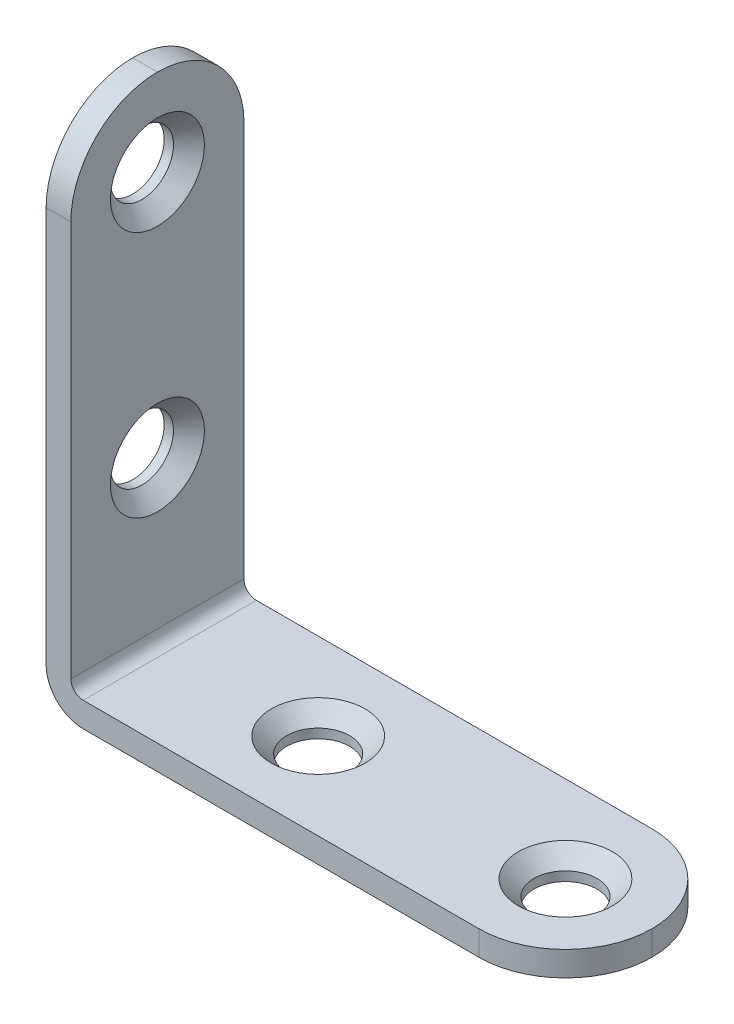
SolidWorks part; units mm, degrees
material "Acier non allié"
ref_plane "Plan de face" through (0, 0, 0) normal (0, 0, 1) x (1, 0, 0)
ref_plane "Plan de dessus" through (0, 0, 0) normal (0, 1, 0) x (1, 0, 0)
ref_plane "Plan de droite" through (0, 0, 0) normal (1, 0, 0) x (0, 0, -1)
sketch "Esquisse1" plane through (0, 0, 0) normal (0, 0, 1) x (1, 0, 0)
  line L0 (0, 3) -> (0, 42)
  line L1 (3, 0) -> (42, 0)
  line L2 (3, 2) -> (42, 2)
  line L3 (2, 3) -> (2, 42)
  line L4 (0, 42) -> (2, 42)
  line L5 (42, 2) -> (42, 0)
  arc A0 (0, 3) -> (3, 0) centre (3, 3) ccw
  arc A1 (2, 3) -> (3, 2) centre (3, 3) ccw
  point P6 (0, 0)
  dimension "D2" = 3
  dimension "D1" = 42
  dimension "D4" = 42
  dimension "D3" = 2
extrude "Boss.-Extru.1" add sketch "Esquisse1" along normal mid plane 14
fillet "Congé1" radius 7 4 edges at (1, 42, -7) (1, 42, 7) (42, 1, -7) (42, 1, 7)
hole_wizard "Fraisage pour vis à tête fraisée à 6 pans creux M51" positions "Esquisse3" profile "Esquisse2" countersink size "M5" standard "ISO" end condition through all
sketch "Esquisse3" plane through (0, 2, 0) normal (0, 1, 0) x (1, 0, 0)
  line L0 (35, 0) -> (15, 0) construction
  point P0 (35, 0)
  point P3 (15, 0)
  dimension "D1" = 20
sketch "Esquisse2" plane through (35, 2, 0) normal (1, 0, 0) x (0, 0, 1)
  line L0 (0, 0) -> (0, 2)
  line L1 (0, 2) -> (2.55, 2)
  line L2 (2.55, 2) -> (2.55, 1.25)
  line L3 (2.55, 1.25) -> (3.8, 0)
  line L5 (3.8, 0) -> (0, 0)
  line L6 (-2.55, 1.25) -> (-3.8, 0) construction
  line L11 (0, -6.35) -> (0, 107.95) construction
  dimension "Diamètre du perçage jusqu'au prochain" = 5.1
  dimension "Profondeur du perçage jusqu'au prochain" = 2
  dimension "Diamètre du fraisage entrant" = 7.6
  dimension "Angle du fraisage entrant" = 90
hole_wizard "Fraisage pour vis à tête fraisée à 6 pans creux M52" positions "Esquisse5" profile "Esquisse4" countersink size "M5" standard "ISO" end condition through all
sketch "Esquisse5" plane through (2, 0, 0) normal (1, 0, 0) x (0, 0, -1)
  line L0 (0, 35) -> (0, 15) construction
  point P0 (0, 35)
  point P3 (0, 15)
  dimension "D1" = 20
sketch "Esquisse4" plane through (2, 35, 0) normal (0, 1, 0) x (0, 0, -1)
  line L0 (0, 0) -> (0, 2)
  line L1 (0, 2) -> (2.55, 2)
  line L2 (2.55, 2) -> (2.55, 1.25)
  line L3 (2.55, 1.25) -> (3.8, 0)
  line L5 (3.8, 0) -> (0, 0)
  line L6 (-2.55, 1.25) -> (-3.8, 0) construction
  line L11 (0, -6.35) -> (0, 107.95) construction
  dimension "Diamètre du perçage jusqu'au prochain" = 5.1
  dimension "Profondeur du perçage jusqu'au prochain" = 2
  dimension "Diamètre du fraisage entrant" = 7.6
  dimension "Angle du fraisage entrant" = 90
